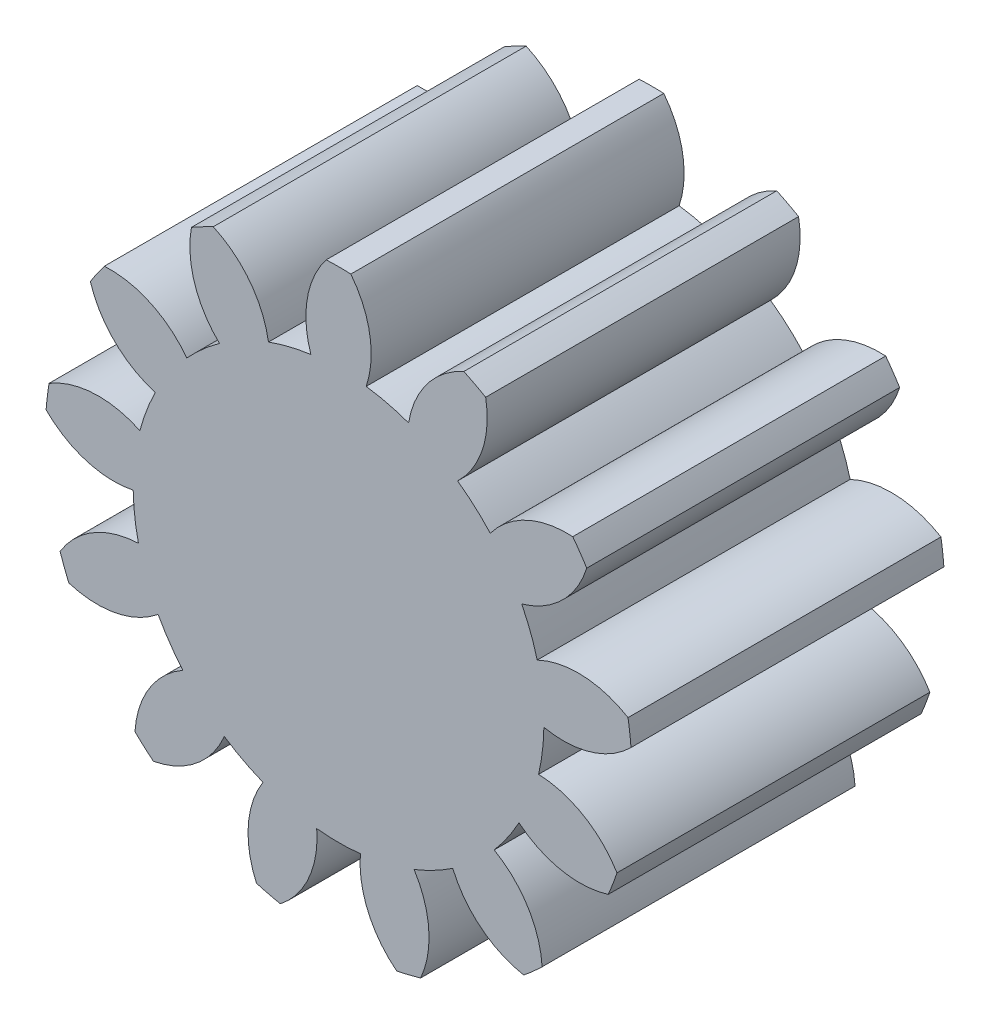
SolidWorks part; units mm, degrees
ref_plane "Front" through (0, 0, 0) normal (0, 0, 1) x (1, 0, 0)
ref_plane "Top" through (0, 0, 0) normal (0, 1, 0) x (1, 0, 0)
ref_plane "Right" through (0, 0, 0) normal (1, 0, 0) x (0, 0, -1)
sketch "Sketch1" plane through (0, 0, 0) normal (0, 0, 1) x (1, 0, 0)
  circle A0 centre (0, 0) radius 52.5
  dimension "D1" = 105
extrude "Base-Extrude" add sketch "Sketch1" against normal blind 80
sketch "Sketch2" plane through (0, 0, 0) normal (0, 0, 1) x (1, 0, 0)
  line L0 (0, 0) -> (0, 64.7411) construction
  line L1 (-8.1143, 63.2315) -> (8.1143, 63.2315) construction
  line L2 (-7.0741, 52.0212) -> (7.0741, 52.0212)
  circle A0 centre (0, 0) radius 52.5 construction
  arc A1 (-7.0741, 52.0212) -> (-3.1481, 74.9339) centre (16.1691, 59.8313) cw
  arc A2 (3.1481, 74.9339) -> (-3.1481, 74.9339) centre (0, 0) ccw
  arc A3 (7.0741, 52.0212) -> (3.1481, 74.9339) centre (-16.1691, 59.8313) ccw
  circle A4 centre (0, 0) radius 63.75 construction
  dimension "D1" = 127.5
  dimension "D2" = 150.0001
  dimension "D3" = 3.1481
  dimension "D4" = 8.1143
  dimension "D5" = 7.0741
extrude "Boss-Extrude1" add sketch "Sketch2" against normal up to surface (80 mm away) up to face at (52.5, 0, -80)
ref_axis "Axis1" through (0, 0, -84) along (0, 0, 1)
pattern_circular "CirPattern1" count 13 every 27.692 about axis through (0, 0, -84) along (0, 0, 1) of "Boss-Extrude1"
ref_plane "Plane1" through (65, 0, 0) normal (1, 0, 0) x (0, 0, -1)
ref_axis "AxisDistance" through (65, 0, 4) along (0, 0, -1)
ref_plane "MidPlane" through (0, 0, -40) normal (0, 0, 1) x (1, 0, 0)
equation "\"D2@CirPattern1\" = 360/\"D1@CirPattern1\""
equation "\"D1@MidPlane\"=\"D1@Base-Extrude\"/2"
